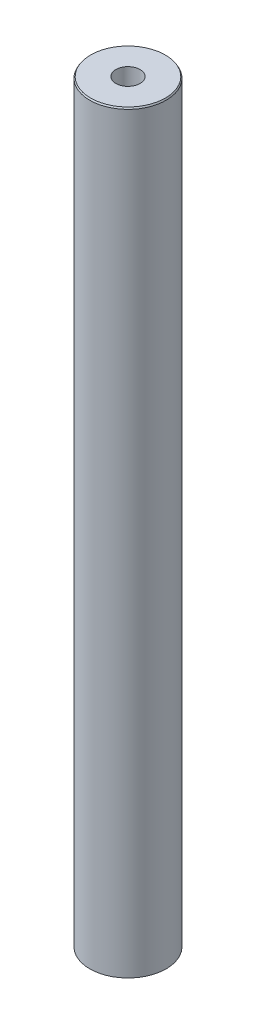
SolidWorks part; units mm, degrees
ref_plane "Front Plane" through (0, 0, 0) normal (0, 0, 1) x (1, 0, 0)
ref_plane "Top Plane" through (0, 0, 0) normal (0, 1, 0) x (1, 0, 0)
ref_plane "Right Plane" through (0, 0, 0) normal (1, 0, 0) x (0, 0, -1)
sketch "Sketch1" plane through (0, 0, 0) normal (0, 1, 0) x (1, 0, 0)
  circle A0 centre (0, 0) radius 7.5
  dimension "SHAFT_OD" = 15
extrude "Boss-Extrude1" add sketch "Sketch1" along normal blind 148.1335
sketch "Sketch2" plane through (0, 0, 0) normal (0, 1, 0) x (1, 0, 0)
  circle A0 centre (0, 0) radius 2.3777
  dimension "BORE_D" = 4.7554
extrude "Cut-Extrude1" cut sketch "Sketch2" along normal through all
chamfer "Chamfer1" distance 0.2877 angle 30 2 edges at (0, 148.1335, 7.5) (0, 0, 7.5) first distance on face at (0, 148.1335, 7.5) first distance on face at (0, 0, 2.3777)
